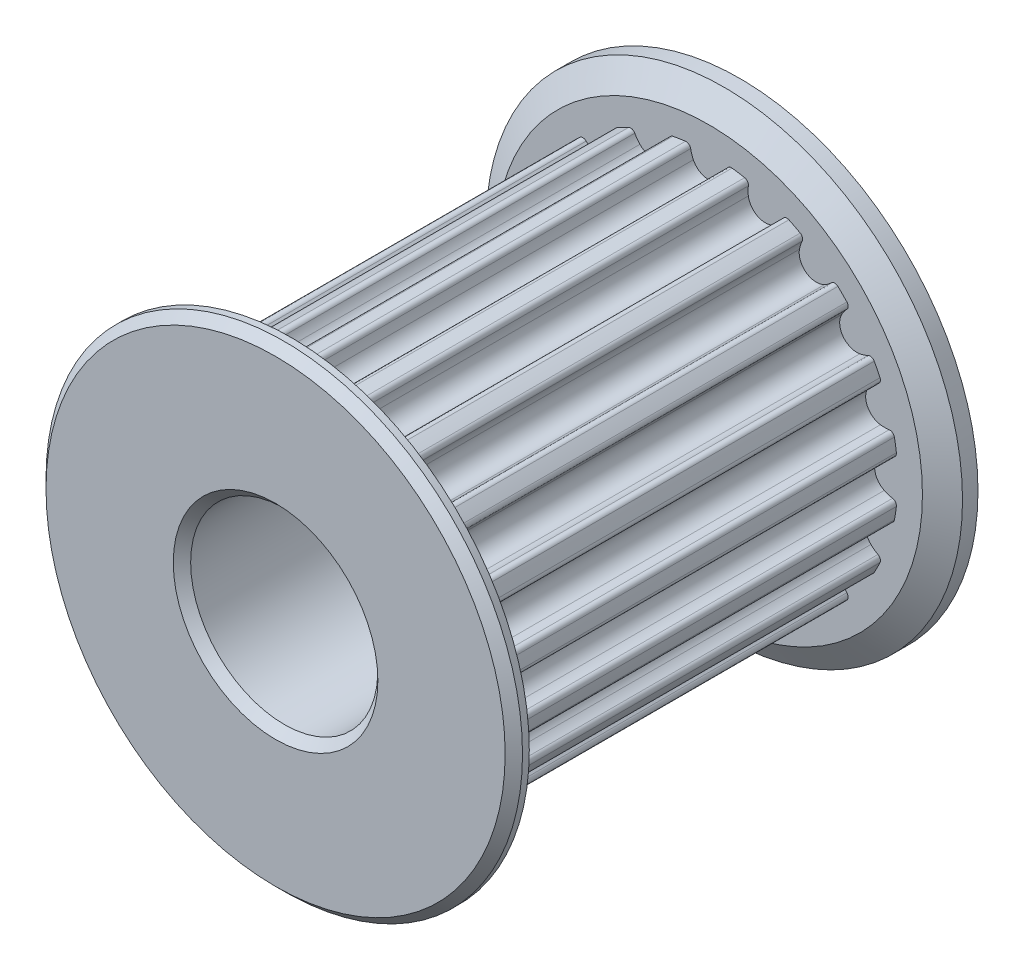
SolidWorks part; units mm, degrees
ref_plane "Front Plane" through (0, 0, 0) normal (0, 0, 1) x (1, 0, 0)
ref_plane "Top Plane" through (0, 0, 0) normal (0, 1, 0) x (1, 0, 0)
ref_plane "Right Plane" through (0, 0, 0) normal (1, 0, 0) x (0, 0, -1)
sketch "Sketch1" plane through (0, 0, 0) normal (0, 0, 1) x (1, 0, 0)
  line L1 (-1.7499, 5.3585) -> (1.7499, 5.3585) construction
  line L4 (0, 0) -> (0, 5.3585) construction
  line L5 (0, 5.3585) -> (0, 11.2107) construction
  line L6 (0, 6.3625) -> (1.9751, 6.0482) construction
  line L7 (1.9751, 6.0482) -> (2.6648, 5.8229) construction
  line L8 (1.9751, 6.0482) -> (1.7499, 5.3585) construction
  line L9 (-1.9751, 6.0482) -> (-1.7499, 5.3585) construction
  line L10 (-1.8963, 5.8067) -> (-2.5144, 7.6995)
  line L11 (-2.5144, 7.6995) -> (2.5144, 7.6995)
  line L12 (2.5144, 7.6995) -> (1.8963, 5.8067)
  circle A0 centre (0, 0) radius 6.3625 construction
  circle A1 centre (0, 0) radius 7.6995 construction
  circle A2 centre (0, 0) radius 6.1085 construction
  arc A3 (-0.4989, 5.6703) -> (0.4989, 5.6703) centre (0, 5.9135) ccw
  arc A4 (-0.4989, 5.6703) -> (-0.5855, 5.9387) centre (0.4, 6.1085) cw
  arc A5 (-1.8963, 5.8067) -> (-0.7518, 6.0621) centre (0, 0) cw
  arc A6 (-0.5855, 5.9387) -> (-0.7518, 6.0621) centre (-0.7333, 5.9132) ccw
  arc A7 (1.8963, 5.8067) -> (0.7518, 6.0621) centre (0, 0) ccw
  arc A8 (0.5855, 5.9387) -> (0.7518, 6.0621) centre (0.7333, 5.9132) cw
  arc A9 (0.4989, 5.6703) -> (0.5855, 5.9387) centre (-0.4, 6.1085) ccw
  point P6 (0, 20.9083)
  point P11 (0, 6.3625)
  point P13 (0, 7.6995)
  point P14 (0, 6.1085)
  dimension "D1" = 9.6976
  dimension "PD" = 12.725
  dimension "D2" = 4.8482
  dimension "OD" = 15.399
  dimension "R3" = 0.555
  dimension "R2" = 1
  dimension "R1" = 0.15
  dimension "b" = 0.4
  dimension "D3" = 2
  dimension "PLD" = 0.254
  dimension "h" = 0.75
sketch "Sketch2" plane through (0, 0, 0) normal (1, 0, 0) x (0, 0, -1)
  line L0 (-7.5, 3.025) -> (7.5, 3.025)
  line L1 (-7.5, 3.025) -> (-7.5, 7.6995)
  line L2 (-7, 7.6995) -> (-7.5, 7.6995)
  line L3 (-7.5, 3.025) -> (-7.5, 7.6995) construction
  line L4 (-7.5, 7.6995) -> (-6.5, 7.6995) construction
  line L5 (-6.5, 7.6995) -> (-6.5, 6.1085) construction
  line L6 (-6.5, 6.1085) -> (6.5, 6.1085)
  line L7 (6.5, 6.1085) -> (6.5, 7.6995) construction
  line L8 (6.5, 7.6995) -> (7.5, 7.6995) construction
  line L9 (7.5, 7.6995) -> (7.5, 3.025)
  line L10 (-7.5, 0) -> (7.5, 0) construction
  line L11 (7, 7.6995) -> (6.5, 6.904)
  line L12 (-6.5, 6.904) -> (-7, 7.6995)
  line L14 (-6.5, 6.904) -> (-6.5, 6.1085)
  line L15 (6.5, 6.1085) -> (6.5, 6.904)
  line L16 (7, 7.6995) -> (7.5, 7.6995)
  arc A0 (-6.5, 6.904) -> (-7, 7.6995) centre (-7.3828, 6.904) ccw construction
  arc A1 (6.5, 6.904) -> (7, 7.6995) centre (7.3828, 6.904) cw construction
  point P12 (-6.5, 6.904)
  point P14 (-7, 7.6995)
  point P20 (6.5, 6.904)
  point P21 (7, 7.6995)
  point P25 (6.5, 0)
  point P26 (-6.5, 0)
  dimension "OA" = 15
  dimension "Bore" = 6.05
  dimension "Outside Width" = 14
  dimension "Inside Width" = 13
revolve "Revolve1" add sketch "Sketch2" angle 360 mid plane about L10
sketch "Sketch3" plane through (0, 0, 0) normal (0, 0, 1) x (1, 0, 0)
  line L6 (2.5144, 7.6995) -> (-2.5144, 7.6995)
  line L7 (1.8963, 5.8067) -> (2.5144, 7.6995)
  line L8 (-2.5144, 7.6995) -> (-1.8963, 5.8067)
  line L9 (2.5144, 7.6995) -> (-2.5144, 7.6995)
  line L10 (1.8963, 5.8067) -> (2.5144, 7.6995)
  line L11 (-2.5144, 7.6995) -> (-1.8963, 5.8067)
  arc A8 (1.8963, 5.8067) -> (0.7518, 6.0621) centre (0, 0) ccw
  arc A9 (0.7518, 6.0621) -> (0.5855, 5.9387) centre (0.7333, 5.9132) ccw
  arc A10 (0.4989, 5.6703) -> (0.5855, 5.9387) centre (-0.4, 6.1085) ccw
  arc A11 (-0.4989, 5.6703) -> (0.4989, 5.6703) centre (0, 5.9135) ccw
  arc A12 (-0.5855, 5.9387) -> (-0.4989, 5.6703) centre (0.4, 6.1085) ccw
  arc A13 (-0.5855, 5.9387) -> (-0.7518, 6.0621) centre (-0.7333, 5.9132) ccw
  arc A14 (-0.7518, 6.0621) -> (-1.8963, 5.8067) centre (0, 0) ccw
  arc A15 (1.8963, 5.8067) -> (0.7518, 6.0621) centre (0, 0) ccw
  arc A16 (0.7518, 6.0621) -> (0.5855, 5.9387) centre (0.7333, 5.9132) ccw
  arc A17 (0.4989, 5.6703) -> (0.5855, 5.9387) centre (-0.4, 6.1085) ccw
  arc A18 (-0.4989, 5.6703) -> (0.4989, 5.6703) centre (0, 5.9135) ccw
  arc A19 (-0.5855, 5.9387) -> (-0.4989, 5.6703) centre (0.4, 6.1085) ccw
  arc A20 (-0.5855, 5.9387) -> (-0.7518, 6.0621) centre (-0.7333, 5.9132) ccw
  arc A21 (-0.7518, 6.0621) -> (-1.8963, 5.8067) centre (0, 0) ccw
  dimension "D1" = 0
extrude "Cut-Extrude1" cut sketch "Sketch3" against normal up to vertex (6.5 mm away) from vertex up to point (0, 6.1085, -6.5) starting at point (0, 6.1085, 6.5)
pattern_circular "CirPattern1" count 20 over 360 about axis through (0, 0, 7.5) along (0, 0, 1) of "Cut-Extrude1"
sketch "Sketch4" plane through (0, 0, 0) normal (1, 0, 0) x (0, -1, 0)
  line L0 (0, -6.5) -> (0, -7.5) construction
  line L1 (-3.025, -7.5) -> (3.025, -7.5) construction
  line L2 (6.904, -6.5) -> (-6.904, -6.5) construction
  circle A0 centre (0, -7) radius 1.7526
  dimension "Set Screw" = 3.5052
ref_plane "Plane1" through (0, 0, 7) normal (0, 0, 1) x (1, 0, 0)
chamfer "Chamfer1" distance 0.2807 angle 45 2 edges at (3.025, 0, 7.5) (7.6995, 0, 7.5)
ref_axis "Center Axis 1" through (0, 0, -7.5) along (0, 0, 1)
ref_plane "Contact Plane 1" through (0, 0, 7.5) normal (0, 0, 1) x (1, 0, 0)
ref_plane "Contact Plane 2" through (0, 0, -7.5) normal (0, 0, -1) x (-1, 0, 0)
sketch "Sketch5" plane through (0, 0, -7.5) normal (0, 0, -1) x (-1, 0, 0)
  line L0 (-1.6658, -2.525) -> (1.6658, -2.525)
  line L1 (-1.6658, -2.525) -> (-1.6658, -3.025)
  line L2 (-1.6658, -3.025) -> (1.6658, -3.025)
  line L3 (1.6658, -3.025) -> (1.6658, -2.525)
  circle A0 centre (0, 0) radius 3.025 construction
  dimension "D1" = 2.525
  dimension "D2" = 0.5
extrude "Boss-Extrude1" add sketch "Sketch5" against normal blind 9
